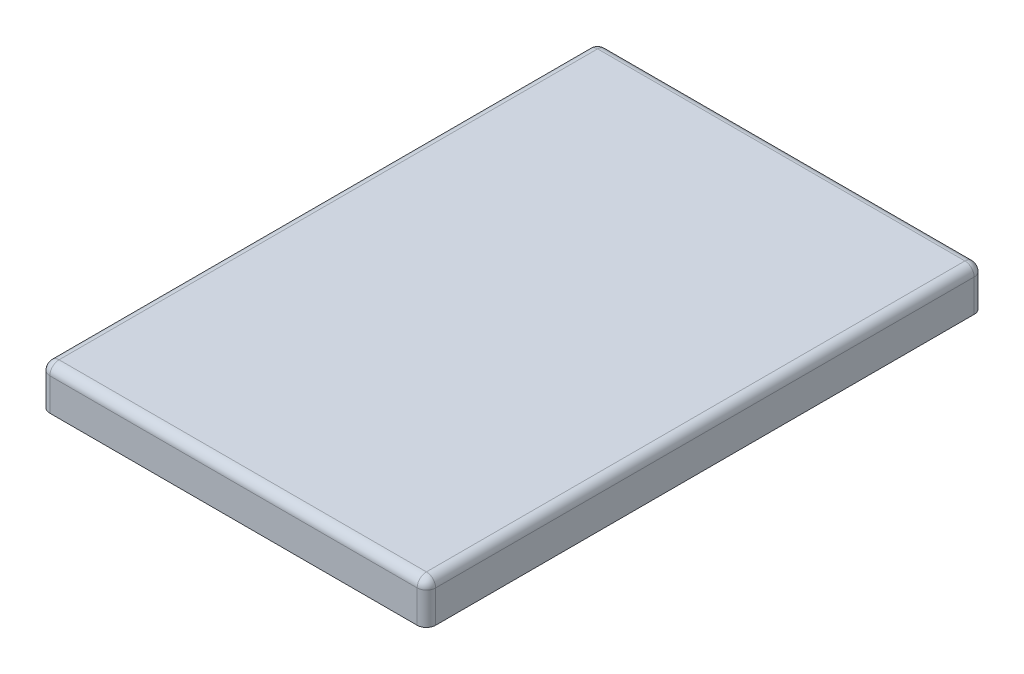
SolidWorks part; units mm, degrees
ref_plane "Front Plane" through (0, 0, 0) normal (0, 0, 1) x (1, 0, 0)
ref_plane "Top Plane" through (0, 0, 0) normal (0, 1, 0) x (1, 0, 0)
ref_plane "Right Plane" through (0, 0, 0) normal (1, 0, 0) x (0, 0, -1)
sketch "Main_Lid" plane through (0, -69.3057, 0) normal (0, 1, 0) x (1, 0, 0)
  line L0 (20.75, -30) -> (20.75, 30.2)
  line L1 (22, -28.75) -> (61.2, -28.75)
  line L2 (22, -28.75) -> (22, 28.95)
  line L3 (22, 28.95) -> (61.2, 28.95)
  line L4 (61.2, -28.75) -> (61.2, 28.95)
  line L5 (20.75, 30.2) -> (62.45, 30.2)
  line L6 (62.45, -30) -> (62.45, 30.2)
  line L7 (20.75, -30) -> (62.45, -30)
  line L9 (20.75, 30.2) -> (62.45, 30.2)
  line L10 (20.75, 30.2) -> (20.75, -30)
  line L11 (20.75, -30) -> (62.45, -30)
  line L12 (62.45, 30.2) -> (62.45, -30)
  dimension "D2" = 39.2
  dimension "D3" = 57.7
  dimension "D1" = 1.25
extrude "Boss-Extrude1" add sketch "Main_Lid" along normal blind 4.5 contours L1 L4 L3 L2 | L0 L7 L6 L5 L4 L1 L2 L3 region at (21.4823, -69.3057, -0.1) region at (41.6, -69.3057, -0.1)
extrude "Cut-Extrude1" cut sketch "Main_Lid<3>" along normal blind 2.65 contours L1 L4 L3 L2 region at (41.6, -69.3057, -0.1)
sketch "Main_Lid<3>" plane through (0, -69.3057, 0) normal (0, 1, 0) x (1, 0, 0) same geometry as "Main_Lid"
sketch "Sketch2" plane through (0, 0, -28.95) normal (0, 0, 1) x (1, 0, 0)
  line L0 (61.2, -66.6557) -> (61.2, -69.3057) construction
  line L1 (41.15, -67.6057) -> (58.2, -67.6057)
  line L2 (41.15, -67.6057) -> (41.15, -68.5057)
  line L3 (41.15, -68.5057) -> (58.2, -68.5057)
  line L4 (58.2, -67.6057) -> (58.2, -68.5057)
  line L5 (20.75, -69.3057) -> (62.45, -69.3057) construction
  dimension "D1" = 0.8
  dimension "D2" = 0.9
  dimension "D3" = 3
  dimension "D4" = 17.05
extrude "Cut-Extrude2" cut sketch "Sketch2" against normal blind 0.75
sketch "Sketch3" plane through (61.2, 0, 0) normal (-1, 0, 0) x (0, 0, 1)
  line L0 (-28.95, -66.6557) -> (-28.95, -69.3057) construction
  line L1 (-18.95, -67.4557) -> (18.75, -67.4557)
  line L2 (-18.95, -67.4557) -> (-18.95, -68.5057)
  line L3 (-18.95, -68.5057) -> (18.75, -68.5057)
  line L4 (18.75, -67.4557) -> (18.75, -68.5057)
  line L5 (28.75, -66.6557) -> (-28.95, -66.6557) construction
  line L6 (-27.5, -69.3057) -> (27.5, -69.3057) construction
  line L7 (28.75, -66.6557) -> (28.75, -69.3057) construction
  point P10 (18.75, -67.9807)
  dimension "D1" = 10
  dimension "D2" = 0.8
  dimension "D3" = 0.8
  dimension "D4" = 10
extrude "Cut-Extrude3" cut sketch "Sketch3" against normal blind 0.75
sketch "Sketch4" plane through (0, 0, 28.75) normal (0, 0, -1) x (-1, 0, 0)
  line L0 (-22, -69.3057) -> (-61.2, -69.3057) construction
  line L1 (-51.2, -67.6057) -> (-32, -67.6057)
  line L2 (-51.2, -67.6057) -> (-51.2, -68.5057)
  line L3 (-51.2, -68.5057) -> (-32, -68.5057)
  line L4 (-32, -67.6057) -> (-32, -68.5057)
  line L5 (-61.2, -66.6557) -> (-61.2, -69.3057) construction
  line L6 (-22, -66.6557) -> (-22, -69.3057) construction
  dimension "D1" = 0.8
  dimension "D2" = 0.9
  dimension "D3" = 10
  dimension "D4" = 10
extrude "Cut-Extrude4" cut sketch "Sketch4" against normal blind 0.75
fillet "Fillet1" radius 1 8 edges at (41.6, -64.8057, -30.2) (41.6, -64.8057, 30) (20.75, -64.8057, -0.1) (20.75, -67.0557, 30) (62.45, -67.0557, 30) (20.75, -67.0557, -30.2) (62.45, -67.0557, -30.2) (62.45, -64.8057, -0.1)
